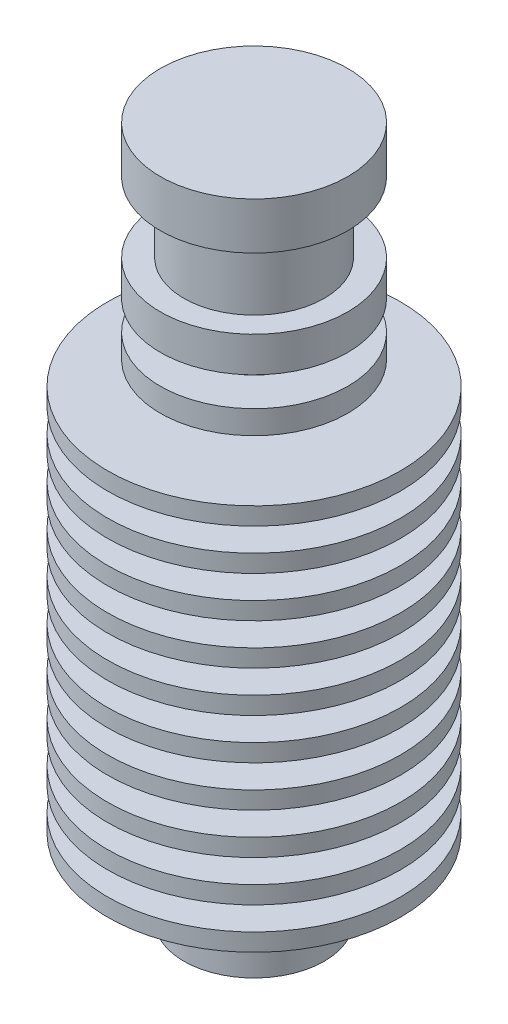
SolidWorks part; units mm, degrees
material "AlMg3 "
ref_plane "xy" through (0, 0, 0) normal (0, 0, 1) x (1, 0, 0)
ref_plane "xz" through (0, 0, 0) normal (0, 1, 0) x (1, 0, 0)
ref_plane "yz" through (0, 0, 0) normal (1, 0, 0) x (0, 0, -1)
ref_axis "x" through (-88.99, 0, 0) along (1, 0, 0)
ref_axis "y" through (0, 55, 0) along (0, -1, 0)
ref_axis "z" through (0, 0, -88.99) along (0, 0, 1)
sketch "Sketch1" plane through (0, 0, 0) normal (0, 0, 1) x (1, 0, 0)
  line L0 (0, -29.5) -> (0, 29.5) construction
  line L1 (0, 29.5) -> (8, 29.5)
  line L2 (8, 29.5) -> (8, 25.5)
  line L3 (8, 25.5) -> (6, 25.5)
  line L4 (6, 25.5) -> (6, 19.5)
  line L5 (6, 19.5) -> (8, 19.5)
  line L6 (8, 19.5) -> (8, 16.5)
  line L7 (8, 16.5) -> (4.5, 16.5)
  line L8 (4.5, 16.5) -> (4.5, 14)
  line L9 (4.5, 14) -> (8, 14)
  line L10 (8, 14) -> (8, 12)
  line L11 (8, 12) -> (4.5, 12)
  line L12 (4.5, 12) -> (4.5, 10)
  line L13 (4.5, 10) -> (12.5, 10)
  line L14 (12.5, 10) -> (12.5, 8.5)
  line L15 (12.5, 8.5) -> (4.5, 8.5)
  line L16 (4.5, 8.5) -> (4.5, 6.5)
  line L17 (4.5, 6.5) -> (12.5, 6.5)
  line L18 (12.5, 6.5) -> (12.5, 5)
  line L19 (12.5, 5) -> (4.5, 5)
  line L20 (4.5, 5) -> (4.5, 3)
  line L21 (4.5, 3) -> (12.5, 3)
  line L22 (12.5, 3) -> (12.5, 1.5)
  line L23 (12.5, 1.5) -> (4.5, 1.5)
  line L24 (4.5, 1.5) -> (4.5, -0.5)
  line L25 (4.5, -0.5) -> (12.5, -0.5)
  line L26 (12.5, -0.5) -> (12.5, -2)
  line L27 (12.5, -2) -> (6.5, -2)
  line L28 (6.5, -2) -> (6.5, -4)
  line L29 (6.5, -4) -> (12.5, -4)
  line L30 (12.5, -4) -> (12.5, -5.5)
  line L31 (12.5, -5.5) -> (7.5, -5.5)
  line L32 (7.5, -5.5) -> (7.5, -7.5)
  line L33 (7.5, -7.5) -> (12.5, -7.5)
  line L34 (12.5, -7.5) -> (12.5, -9)
  line L35 (12.5, -9) -> (7.5, -9)
  line L36 (7.5, -9) -> (7.5, -11)
  line L37 (7.5, -11) -> (12.5, -11)
  line L38 (12.5, -11) -> (12.5, -12.5)
  line L39 (12.5, -12.5) -> (7.5, -12.5)
  line L40 (7.5, -12.5) -> (7.5, -14.5)
  line L41 (7.5, -14.5) -> (12.5, -14.5)
  line L42 (12.5, -14.5) -> (12.5, -16)
  line L43 (12.5, -16) -> (7.5, -16)
  line L44 (7.5, -16) -> (7.5, -18)
  line L45 (12.5, -18) -> (12.5, -19.5)
  line L46 (12.5, -19.5) -> (7.5, -19.5)
  line L47 (7.5, -19.5) -> (7.5, -21.5)
  line L48 (7.5, -21.5) -> (12.5, -21.5)
  line L49 (7.5, -18) -> (12.5, -18)
  line L50 (12.5, -21.5) -> (12.5, -23)
  line L51 (12.5, -23) -> (4, -23)
  line L52 (4, -23) -> (4, -25)
  line L53 (4, -25) -> (6, -25)
  line L54 (6, -25) -> (6, -29.5)
  line L55 (6, -29.5) -> (0, -29.5)
  line L56 (0, 29.5) -> (0, -29.5)
  point P4 (0, 0)
  point P32 (12.5, 9.25)
  point P50 (12.5, -4.75)
  dimension "D1" = 8
  dimension "D2" = 6
  dimension "D3" = 4
  dimension "D4" = 6
  dimension "D5" = 2.5
  dimension "D6" = 3
  dimension "D7" = 12.5
  dimension "D8" = 8
  dimension "D9" = 2
  dimension "D10" = 1.5
  dimension "D11" = 2
  dimension "D12" = 6
  dimension "D13" = 5
  dimension "D14" = 6.5
  dimension "D15" = 2
  dimension "D16" = 6
  dimension "D17" = 4
  dimension "D18" = 4.5
revolve "Revolve1" add sketch "Sketch1" angle 360 about L0
